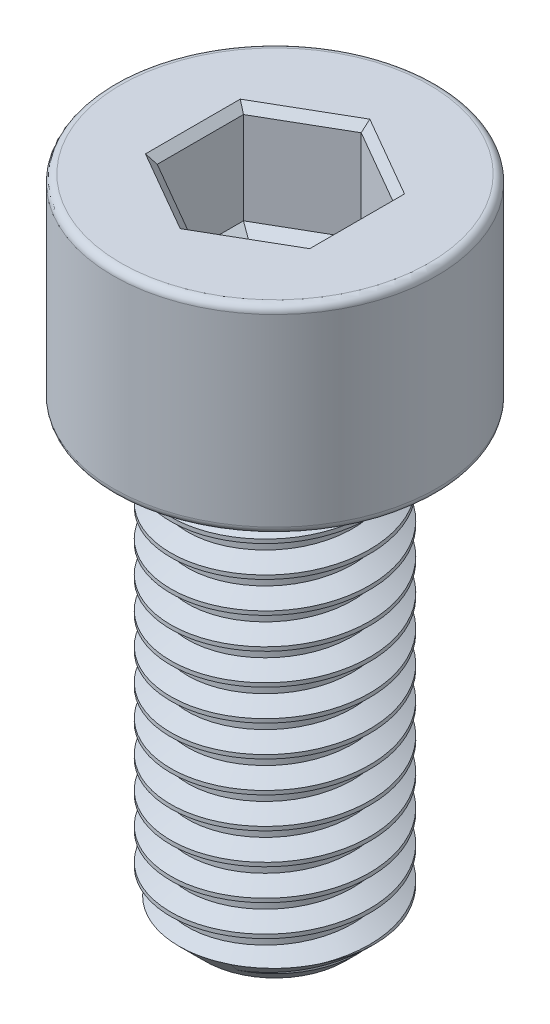
SolidWorks part; units mm, degrees
material "AISI Type A2 Tool Steel"
ref_plane "Front Plane" through (0, 0, 0) normal (0, 0, 1) x (1, 0, 0)
ref_plane "Top Plane" through (0, 0, 0) normal (0, 1, 0) x (1, 0, 0)
ref_plane "Right Plane" through (0, 0, 0) normal (1, 0, 0) x (0, 0, -1)
sketch "Sketch1" plane through (0, 0, 0) normal (0, 1, 0) x (1, 0, 0)
  circle A0 centre (0, 0) radius 4
  dimension "D1" = 8
extrude "Boss-Extrude1" add sketch "Sketch1" along normal blind 18
thread "Thread1" pitch 1.25 method cut profile "Thread Profile1" start angle 0, offset 1.25, length 0, pitch 1.25, diameter 8
ref_plane "Plane1" through (-4, 19.25, 0) normal (0, 0, 1) x (-1, 0, 0)
sketch "Thread Profile1" plane through (-4, 19.25, 0) normal (0, 0, 1) x (-1, 0, 0)
  line L0 (0, 0) -> (0, 1.25) construction
  line L11 (0, 0) -> (0, 1.0937)
  line L12 (0, 1.0937) -> (-0.6766, 0.7031)
  line L13 (-0.6766, 0.7031) -> (-0.6766, 0.3906)
  line L15 (-0.6766, 0.3906) -> (0, 0)
  line L17 (-0.6766, 0.5469) -> (0, 0.5469) construction
  point P2 (0, 0)
  dimension "Pitch" = 1.25
  dimension "Profile_Angle" = 60
  dimension "Profile_Land" = 0.3125
  dimension "Profile_Height" = 0.6766
sketch "Sketch2" plane through (0, 18, 0) normal (0, 1, 0) x (1, 0, 0)
  circle A0 centre (0, 0) radius 6.5
  dimension "D1" = 13
extrude "Boss-Extrude2" add sketch "Sketch2" along normal blind 8
sketch "Sketch5" plane through (0, 0, 0) normal (0, 0, 1) x (1, 0, 0)
  line L0 (0, 0) -> (0, 0.9986) construction
  line L1 (0, 0) -> (4.01, 0) construction
  line L2 (4.01, 0) -> (4.01, 1.2)
  line L3 (4.01, 1.2) -> (2.81, 0)
  line L4 (2.81, 0) -> (4.01, 0)
  dimension "D1" = 1.2
  dimension "D2" = 45
  dimension "D3" = 4.01
revolve "Cut-Revolve1" cut sketch "Sketch5" angle 360 about L0
fillet "Fillet1" radius 0.3 2 edges at (0, 26, 6.5) (0, 18, 6.5)
sketch "Sketch6" plane through (0, 26, 0) normal (0, 1, 0) x (1, 0, 0)
  line L1 (0, 3.4641) -> (-3, 1.7321)
  line L2 (-3, 1.7321) -> (-3, -1.7321)
  line L3 (-3, -1.7321) -> (0, -3.4641)
  line L4 (0, -3.4641) -> (3, -1.7321)
  line L5 (3, -1.7321) -> (3, 1.7321)
  line L6 (3, 1.7321) -> (0, 3.4641)
  circle A0 centre (0, 0) radius 3 construction
  dimension "D1" = 6
extrude "Cut-Extrude1" cut sketch "Sketch6" against normal blind 4
chamfer "Chamfer1" distance 0.3 angle 45 6 edges at (-3, 26, 0) (-1.5, 26, 2.5981) (1.5, 26, 2.5981) (3, 26, 0) (1.5, 26, -2.5981) (-1.5, 26, -2.5981)
sketch "Sketch7" plane through (0, 22, 0) normal (0, 1, 0) x (1, 0, 0)
  line L1 (0, 3.4641) -> (-3, 1.7321)
  line L2 (-3, 1.7321) -> (-3, -1.7321)
  line L3 (-3, -1.7321) -> (0, -3.4641)
  line L4 (0, -3.4641) -> (3, -1.7321)
  line L5 (3, -1.7321) -> (3, 1.7321)
  line L6 (3, 1.7321) -> (0, 3.4641)
  circle A0 centre (0, 0) radius 3 construction
extrude "Cut-Extrude2" cut sketch "Sketch7" against normal blind 0.4 draft 60
